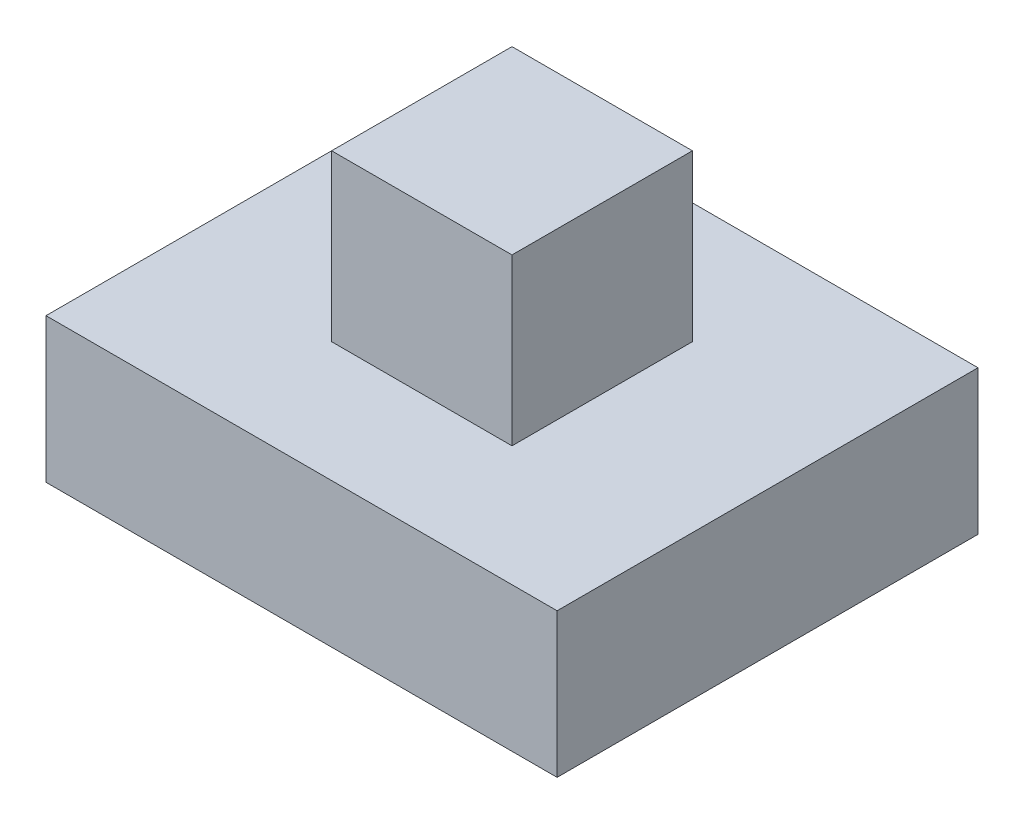
SolidWorks part; units mm, degrees
material "Brass"
ref_plane "Front Plane" through (0, 0, 0) normal (0, 0, 1) x (1, 0, 0)
ref_plane "Top Plane" through (0, 0, 0) normal (0, 1, 0) x (1, 0, 0)
ref_plane "Right Plane" through (0, 0, 0) normal (1, 0, 0) x (0, 0, -1)
sketch "Sketch1" plane through (0, 0, 0) normal (0, 1, 0) x (1, 0, 0)
  line L1 (-4.5, 4.5) -> (4.5, 4.5)
  line L2 (-8.5, 7) -> (8.5, 7)
  line L3 (-8.5, 7) -> (-8.5, -7)
  line L4 (-8.5, -7) -> (8.5, -7)
  line L5 (8.5, 7) -> (8.5, -7)
  line L6 (-8.5, 7) -> (8.5, -7) construction
  line L7 (-8.5, -7) -> (8.5, 7) construction
  line L8 (-4.5, 4.5) -> (-4.5, -4.5)
  line L9 (-4.5, -4.5) -> (4.5, -4.5)
  line L10 (4.5, 4.5) -> (4.5, -4.5)
  line L11 (-4.5, 4.5) -> (4.5, -4.5) construction
  line L12 (-4.5, -4.5) -> (4.5, 4.5) construction
  line L13 (-3, 3) -> (3, 3)
  line L14 (-3, 3) -> (-3, -3)
  line L15 (-3, -3) -> (3, -3)
  line L16 (3, 3) -> (3, -3)
  line L17 (-3, 3) -> (3, -3) construction
  line L18 (-3, -3) -> (3, 3) construction
  point P0 (0, 0)
  point P1 (0, 0)
  point P11 (0, 0)
  dimension "D1" = 17
  dimension "D2" = 14
  dimension "D3" = 9
  dimension "D4" = 9
  dimension "D5" = 6
  dimension "D6" = 6
extrude "Boss-Extrude1" add sketch "Sketch1" against normal blind 4.8 contours L5 L2 L3 L4 L1 L10 L9 L8 | L10 L1 L8 L9 L13 L16 L15 L14 | L16 L13 L14 L15 region at (0, 0, -4.3727) region at (0, 0, -6.7798) region at (0, 0, 0)
extrude "Cut-Extrude1" cut sketch "Sketch1<6>" along normal blind 3 from offset 4.8 contours L16 L13 L14 L15 | L10 L1 L8 L9 L13 L16 L15 L14 region at (0, 0, -4.3727) region at (0, 0, 0) offset against normal yes
sketch "Sketch1<6>" plane through (0, 0, 0) normal (0, 1, 0) x (1, 0, 0) same geometry as "Sketch1"
extrude "Boss-Extrude2" add sketch "Sketch1<3>" along normal blind 5.5 contours L16 L13 L14 L15 region at (0, 0, 0)
sketch "Sketch1<3>" plane through (0, 0, 0) normal (0, 1, 0) x (1, 0, 0) same geometry as "Sketch1"
